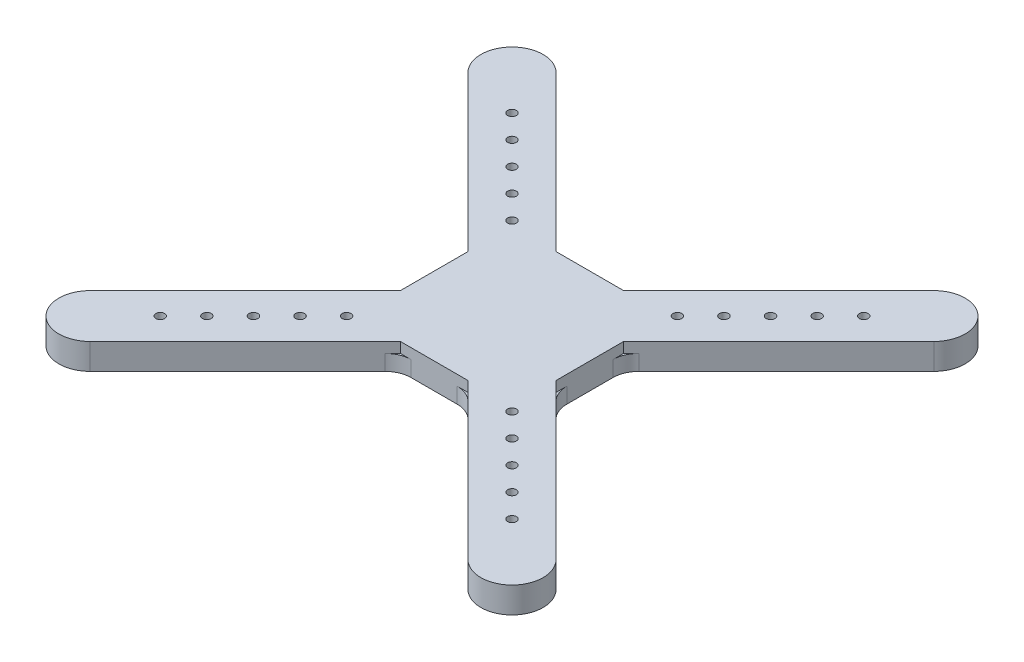
SolidWorks part; units mm, degrees
ref_plane "Front Plane" through (0, 0, 0) normal (0, 0, 1) x (1, 0, 0)
ref_plane "Top Plane" through (0, 0, 0) normal (0, 1, 0) x (1, 0, 0)
ref_plane "Right Plane" through (0, 0, 0) normal (1, 0, 0) x (0, 0, -1)
sketch "Sketch1" plane through (0, 0, 0) normal (0, 1, 0) x (1, 0, 0)
  line L0 (-81.3173, 81.3173) -> (81.3173, -81.3173) construction
  line L1 (-98.425, -98.425) -> (98.425, -98.425) construction
  line L2 (-98.425, -98.425) -> (-98.425, 98.425) construction
  line L3 (-98.425, 98.425) -> (98.425, 98.425) construction
  line L4 (98.425, -98.425) -> (98.425, 98.425) construction
  line L5 (-98.425, -98.425) -> (98.425, 98.425) construction
  line L6 (-98.425, 98.425) -> (98.425, -98.425) construction
  line L7 (-72.832, 89.8026) -> (-13.0294, 30)
  line L8 (-89.8026, 72.832) -> (-30, 13.0294)
  line L9 (0, 98.425) -> (0, -98.425) construction
  line L10 (81.3173, 81.3173) -> (-81.3173, -81.3173) construction
  line L11 (72.832, 89.8026) -> (13.0294, 30)
  line L12 (89.8026, 72.832) -> (30, 13.0294)
  line L13 (-30, -13.0294) -> (-89.8026, -72.832)
  line L14 (-13.0294, -30) -> (13.0294, -30)
  line L15 (-30, -13.0294) -> (-30, 13.0294)
  line L16 (-13.0294, 30) -> (13.0294, 30)
  line L17 (30, -13.0294) -> (30, 13.0294)
  line L18 (-30, -30) -> (30, 30) construction
  line L19 (-30, 30) -> (30, -30) construction
  line L20 (-13.0294, -30) -> (-72.832, -89.8026)
  line L21 (30, -13.0294) -> (89.8026, -72.832)
  line L22 (13.0294, -30) -> (72.832, -89.8026)
  arc A0 (-72.832, 89.8026) -> (-89.8026, 72.832) centre (-81.3173, 81.3173) ccw
  arc A1 (72.832, -89.8026) -> (89.8026, -72.832) centre (81.3173, -81.3173) ccw
  circle A2 centre (-81.3173, 81.3173) radius 8 construction
  circle A3 centre (81.3173, -81.3173) radius 8 construction
  circle A4 centre (-81.3173, -81.3173) radius 8 construction
  circle A5 centre (81.3173, 81.3173) radius 8 construction
  arc A6 (72.832, 89.8026) -> (89.8026, 72.832) centre (81.3173, 81.3173) cw
  arc A7 (-72.832, -89.8026) -> (-89.8026, -72.832) centre (-81.3173, -81.3173) cw
  circle A8 centre (67.7875, 67.7875) radius 1.7
  circle A9 centre (58.8072, 58.8072) radius 1.7
  circle A10 centre (49.827, 49.827) radius 1.7
  circle A11 centre (40.8467, 40.8467) radius 1.7
  circle A12 centre (31.8665, 31.8665) radius 1.7
  circle A13 centre (67.7875, -67.7875) radius 1.7
  circle A14 centre (58.8072, -58.8072) radius 1.7
  circle A15 centre (49.827, -49.827) radius 1.7
  circle A16 centre (40.8467, -40.8467) radius 1.7
  circle A17 centre (31.8665, -31.8665) radius 1.7
  circle A18 centre (-67.7875, 67.7875) radius 1.7
  circle A19 centre (-58.8072, 58.8072) radius 1.7
  circle A20 centre (-31.8665, 31.8665) radius 1.7
  circle A21 centre (-49.827, 49.827) radius 1.7
  circle A22 centre (-40.8467, 40.8467) radius 1.7
  circle A23 centre (-31.8665, -31.8665) radius 1.7
  circle A24 centre (-58.8072, -58.8072) radius 1.7
  circle A25 centre (-40.8467, -40.8467) radius 1.7
  circle A26 centre (-49.827, -49.827) radius 1.7
  circle A27 centre (-67.7875, -67.7875) radius 1.7
  point P0 (0, 0)
  point P8 (0, 0)
  point P23 (0, 0)
  point P29 (0, 0)
  point P42 (30, 0)
  dimension "D2" = 12
  dimension "D4" = 16
  dimension "D6" = 12
  dimension "D9" = 12
  dimension "D10" = 12
  dimension "D13" = 5
  dimension "D1" = 196.85
  dimension "D3" = 115
  dimension "D5" = 115
  dimension "D7" = 60
  dimension "D8" = 26.0589
  dimension "D11" = 30
  dimension "D12" = 30
extrude "Boss-Extrude1" add sketch "Sketch1" along normal blind 6
fillet "Fillet1" radius 10 8 edges at (-30, 3, -13.0294) (-30, 3, 13.0294) (-13.0294, 3, -30) (13.0294, 3, -30) (30, 3, 13.0294) (30, 3, -13.0294) (13.0294, 3, 30) (-13.0294, 3, 30)
extrude "Boss-Extrude2" add sketch "Sketch1<4>" along normal blind 10
sketch "Sketch1<4>" plane through (0, 0, 0) normal (0, 1, 0) x (1, 0, 0) same geometry as "Sketch1"
